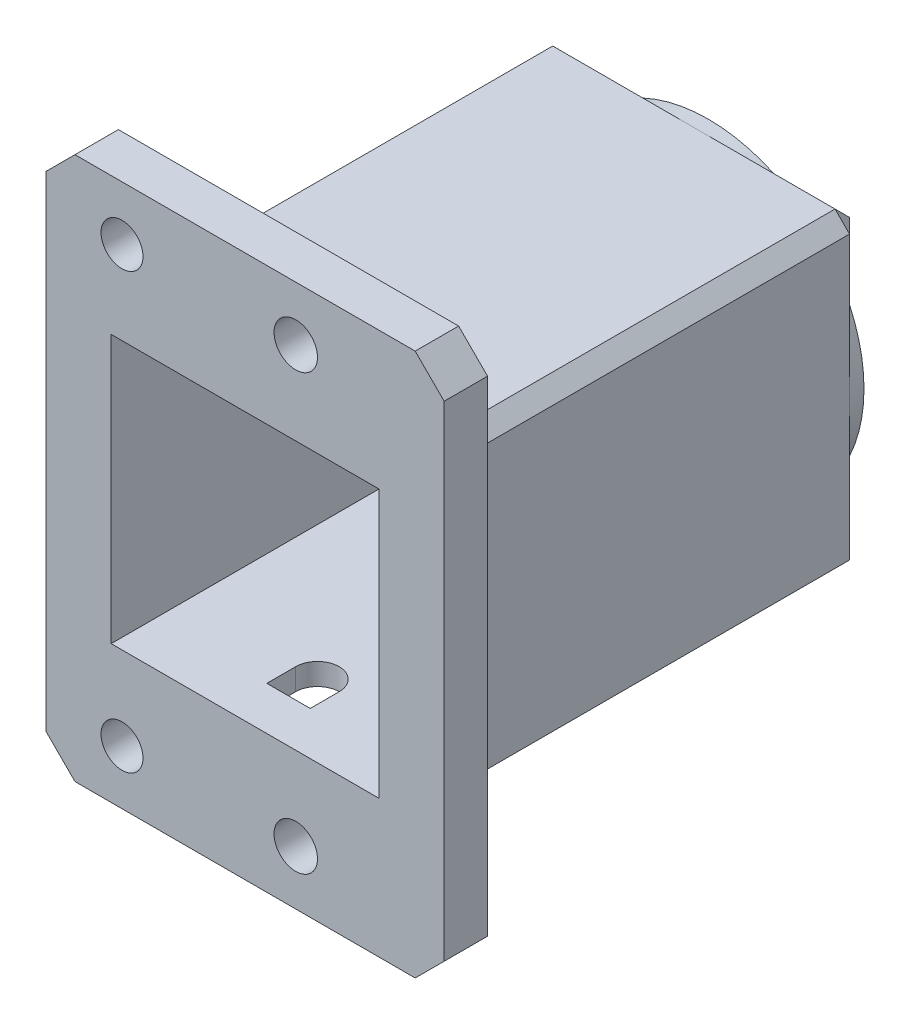
SolidWorks part; units mm, degrees
ref_plane "Front Plane" through (0, 0, 0) normal (0, 0, 1) x (1, 0, 0)
ref_plane "Top Plane" through (0, 0, 0) normal (0, 1, 0) x (1, 0, 0)
ref_plane "Right Plane" through (0, 0, 0) normal (1, 0, 0) x (0, 0, -1)
sketch "Sketch1" plane through (0, 0, 0) normal (0, 0, 1) x (1, 0, 0)
  line L0 (-10.75, 10.75) -> (10.75, 10.75)
  line L1 (-9.25, -9.25) -> (9.25, -9.25) construction
  line L2 (-9.25, -9.25) -> (-9.25, 9.25) construction
  line L3 (-9.25, 9.25) -> (9.25, 9.25) construction
  line L4 (9.25, -9.25) -> (9.25, 9.25) construction
  line L5 (-9.25, -9.25) -> (9.25, 9.25) construction
  line L6 (-9.25, 9.25) -> (9.25, -9.25) construction
  line L7 (10.75, -10.75) -> (10.75, 10.75)
  line L8 (-10.75, -10.75) -> (10.75, -10.75)
  line L9 (-10.75, -10.75) -> (-10.75, 10.75)
  circle A0 centre (0, 0) radius 8 construction
  circle A1 centre (0, 0) radius 8
  circle A2 centre (0, 0) radius 10.75 construction
  circle A3 centre (0, 0) radius 10.75 construction
  dimension "D1" = 18.5
  dimension "D2" = 1.5
extrude "Boss-Extrude1" add sketch "Sketch1" along normal blind 2
sketch "Sketch2" plane through (0, 0, 2) normal (0, 0, 1) x (1, 0, 0)
  line L0 (9.25, -9.25) -> (9.25, 9.25)
  line L1 (9.25, 9.25) -> (-9.25, 9.25)
  line L2 (-9.25, 9.25) -> (-9.25, -9.25)
  line L3 (-9.25, -9.25) -> (9.25, -9.25)
  line L4 (-10.75, 10.75) -> (-10.75, -10.75)
  line L5 (-10.75, -10.75) -> (10.75, -10.75)
  line L6 (10.75, -10.75) -> (10.75, 10.75)
  line L7 (10.75, 10.75) -> (-10.75, 10.75)
  line L8 (-10.75, 10.75) -> (-10.75, -10.75)
  line L9 (-10.75, -10.75) -> (10.75, -10.75)
  line L10 (10.75, -10.75) -> (10.75, 10.75)
  line L11 (10.75, 10.75) -> (-10.75, 10.75)
  dimension "D1" = 0
  dimension "D2" = 1.5
extrude "Boss-Extrude2" add sketch "Sketch2" along normal up to surface (30 mm away)
sketch "Sketch3" plane through (0, 0, 32) normal (0, 0, 1) x (1, 0, 0)
  line L0 (-8.5, 15) -> (-8.5, -15) construction
  line L3 (-13.75, -18.75) -> (13.75, -18.75)
  line L4 (-13.75, -18.75) -> (-13.75, 18.75)
  line L5 (-13.75, 18.75) -> (13.75, 18.75)
  line L6 (-10.75, 10.75) -> (-10.75, -10.75)
  line L7 (-10.75, -10.75) -> (10.75, -10.75)
  line L8 (10.75, -10.75) -> (10.75, 10.75)
  line L9 (10.75, 10.75) -> (-10.75, 10.75)
  line L10 (-10.75, 10.75) -> (-10.75, -10.75)
  line L11 (-10.75, -10.75) -> (10.75, -10.75)
  line L12 (10.75, -10.75) -> (10.75, 10.75)
  line L13 (10.75, 10.75) -> (-10.75, 10.75)
  line L14 (13.75, -18.75) -> (13.75, 18.75)
  line L15 (-13.75, -18.75) -> (13.75, 18.75) construction
  line L16 (-13.75, 18.75) -> (13.75, -18.75) construction
  circle A0 centre (3.5, -15) radius 1.5 construction
  circle A1 centre (3.5, -15) radius 1.5
  circle A2 centre (3.5, 15) radius 1.5 construction
  circle A3 centre (3.5, 15) radius 1.5
  circle A4 centre (-8.5, 15) radius 1.5 construction
  circle A5 centre (-8.5, 15) radius 1.5
  circle A6 centre (-8.5, -15) radius 1.5 construction
  circle A7 centre (-8.5, -15) radius 1.5
  point P12 (0, 0)
  dimension "D1" = 0
  dimension "D2" = 8
  dimension "D3" = 3
extrude "Boss-Extrude3" add sketch "Sketch3" against normal blind 3
sketch "Sketch4" plane through (0, -10.75, 0) normal (0, -1, 0) x (1, 0, 0)
  line L0 (0, 0) -> (0, 29) construction
  line L1 (-13.75, 29) -> (13.75, 29) construction
  line L2 (1.5, 27) -> (1.5, 29)
  line L3 (1.5, 29) -> (-1.5, 29)
  line L4 (-1.5, 29) -> (-1.5, 27)
  circle A0 centre (0, 27) radius 1.5
  line M3 (10.75, 29) -> (-10.75, 29)
  dimension "D1" = 3
  dimension "D2" = 2
extrude "Cut-Extrude1" cut sketch "Sketch4" against normal blind 3 contours A0 L0 | L0 A0 | L0 A0 L2 M3 | A0 L0 L3 L4 region at (-0.6366, -10.75, 27) region at (0.6366, -10.75, 27) region at (-0.9125, -10.75, 28.5209) region at (0.9125, -10.75, 28.5209)
chamfer "Chamfer1" distance 1 angle 45 8 edges at (10.75, -10.75, 14.5) (0, -10.75, 0) (-10.75, -10.75, 14.5) (-10.75, 0, 0) (-10.75, 10.75, 14.5) (0, 10.75, 0) (10.75, 10.75, 14.5) (10.75, 0, 0)
chamfer "Chamfer2" distance 2 angle 45 4 edges at (-13.75, 18.75, 30.5) (-13.75, -18.75, 30.5) (13.75, 18.75, 30.5) (13.75, -18.75, 30.5)
sketch "Sketch5" plane through (0, 0, 29) normal (0, 0, -1) x (-1, 0, 0)
  circle A0 centre (8.5, -15) radius 1.5 construction
  circle A1 centre (8.5, -15) radius 1.5
  circle A2 centre (8.5, 15) radius 1.5 construction
  circle A3 centre (8.5, 15) radius 1.5
  circle A4 centre (8.5, 15) radius 1.45
  circle A5 centre (8.5, -15) radius 1.45
  dimension "D1" = 2.9
  dimension "D2" = 2.9
extrude "Boss-Extrude4" add sketch "Sketch5" against normal up to surface (3 mm away) up to face at (0, 0, 32)
sketch "Sketch6" plane through (0, 0, 0) normal (0, 0, -1) x (-1, 0, 0)
  line L0 (-10.75, -9.75) -> (-10.75, 9.75) construction
  circle A0 centre (0, 0) radius 10.75
  circle A1 centre (0, 0) radius 8 construction
  circle A2 centre (0, 0) radius 8
extrude "Boss-Extrude5" add sketch "Sketch6" against normal blind 1.5
